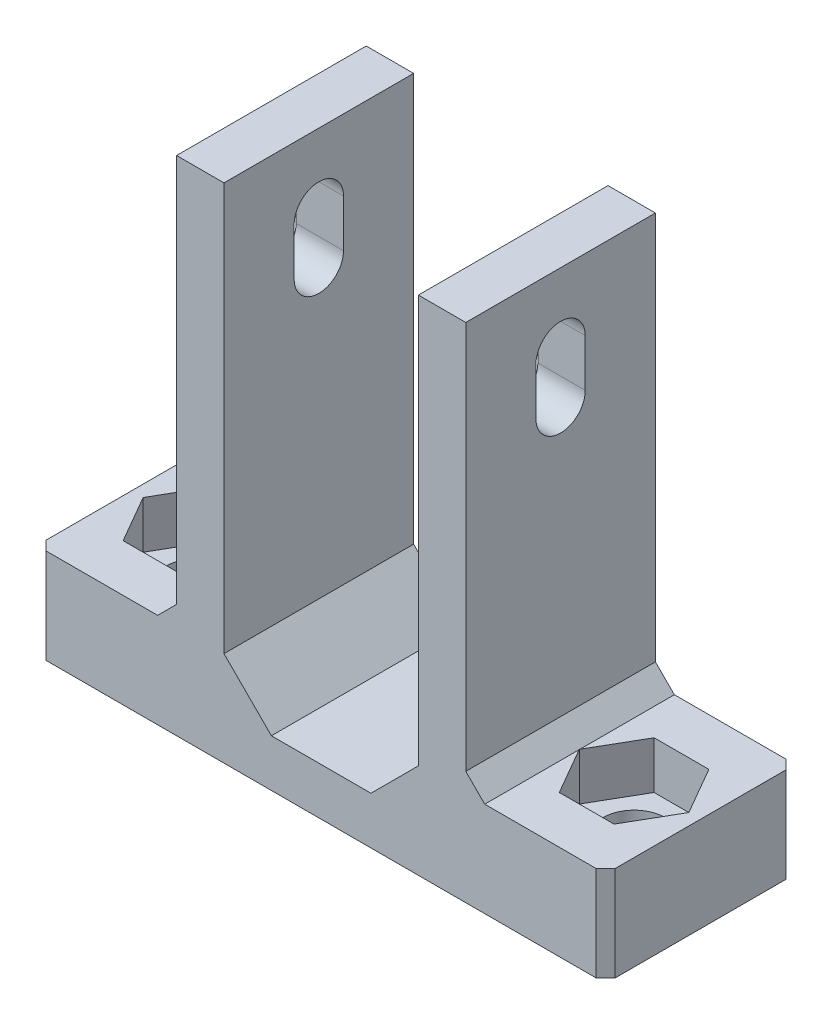
SolidWorks part; units mm, degrees
ref_plane "Front Plane" through (0, 0, 0) normal (0, 0, 1) x (1, 0, 0)
ref_plane "Top Plane" through (0, 0, 0) normal (0, 1, 0) x (1, 0, 0)
ref_plane "Right Plane" through (0, 0, 0) normal (1, 0, 0) x (0, 0, -1)
sketch "Sketch2" plane through (0, 0, 0) normal (0, 1, 0) x (1, 0, 0)
  line L1 (-30, 10) -> (30, 10)
  line L2 (-30, 10) -> (-30, -10)
  line L3 (-30, -10) -> (30, -10)
  line L4 (30, 10) -> (30, -10)
  line L5 (-30, 10) -> (30, -10) construction
  line L6 (-30, -10) -> (30, 10) construction
  circle A0 centre (-23, 0) radius 3.3
  circle A1 centre (23, 0) radius 3.3
  point P0 (0, 0)
  point P10 (0, 0)
  point P11 (0, 0)
  point P12 (0, 0)
  dimension "D5" = 6.6
  dimension "D1" = 20
  dimension "D2" = 60
  dimension "D3" = 46
  dimension "D4" = 23
extrude "Boss-Extrude2" add sketch "Sketch2" along normal blind 5
sketch "Sketch3" plane through (0, 0, 10) normal (0, 0, 1) x (1, 0, 0)
  line L0 (-30, 5) -> (30, 5) construction
  line L1 (-15.25, 5) -> (-10.25, 5)
  line L2 (-15.25, 5) -> (-15.25, 53)
  line L3 (-15.25, 53) -> (-10.25, 53)
  line L4 (-10.25, 5) -> (-10.25, 53)
  line L5 (0, 0) -> (0, -12.3291) construction
  line L6 (10.25, 5) -> (15.25, 5)
  line L7 (10.25, 5) -> (10.25, 53)
  line L8 (10.25, 53) -> (15.25, 53)
  line L9 (15.25, 5) -> (15.25, 53)
  dimension "D1" = 20.5
  dimension "D2" = 5
  dimension "D3" = 48
extrude "Boss-Extrude3" add sketch "Sketch3" against normal up to surface (20 mm away) up to face at (0, 2.5, -10)
sketch "Sketch4" plane through (15.25, 0, 0) normal (1, 0, 0) x (0, 0, -1)
  line L0 (0, 45.5) -> (0, 40.5) construction
  line L1 (2.6, 45.5) -> (2.6, 40.5)
  line L2 (-2.6, 45.5) -> (-2.6, 40.5)
  line L3 (10, 53) -> (-10, 53) construction
  arc A0 (2.6, 45.5) -> (-2.6, 45.5) centre (0, 45.5) ccw
  arc A1 (-2.6, 40.5) -> (2.6, 40.5) centre (0, 40.5) ccw
  point P3 (0, 43)
  dimension "D1" = 5.2
  dimension "D2" = 10
  dimension "D3" = 5
extrude "Cut-Extrude1" cut sketch "Sketch4" against normal up to surface (30.5 mm away) up to face at (-15.25, 29, 0)
sketch "Sketch5" plane through (0, 5, 0) normal (0, 1, 0) x (1, 0, 0)
  line L0 (30, 10) -> (15.25, 10) construction
  line L1 (15.25, 10) -> (15.25, -10) construction
  line L2 (15.25, -10) -> (30, -10) construction
  line L3 (30, -10) -> (30, 10) construction
  line L4 (-15.25, -10) -> (-15.25, 10) construction
  line L5 (-15.25, 10) -> (-30, 10) construction
  line L6 (-30, 10) -> (-30, -10) construction
  line L7 (-30, -10) -> (-15.25, -10) construction
  line L8 (30, 10) -> (15.25, 10)
  line L9 (15.25, 10) -> (15.25, -10)
  line L10 (15.25, -10) -> (30, -10)
  line L11 (30, -10) -> (30, 10)
  line L12 (-15.25, -10) -> (-15.25, 10)
  line L13 (-15.25, 10) -> (-30, 10)
  line L14 (-30, 10) -> (-30, -10)
  line L15 (-30, -10) -> (-15.25, -10)
  line L17 (-17.2265, 0) -> (-20.1132, 5)
  line L18 (-20.1132, 5) -> (-25.8868, 5)
  line L19 (-25.8868, 5) -> (-28.7735, 0)
  line L20 (-28.7735, 0) -> (-25.8868, -5)
  line L21 (-25.8868, -5) -> (-20.1132, -5)
  line L22 (-20.1132, -5) -> (-17.2265, 0)
  line L23 (28.7735, 0) -> (25.8868, 5)
  line L24 (25.8868, 5) -> (20.1132, 5)
  line L25 (20.1132, 5) -> (17.2265, 0)
  line L26 (17.2265, 0) -> (20.1132, -5)
  line L27 (20.1132, -5) -> (25.8868, -5)
  line L28 (25.8868, -5) -> (28.7735, 0)
  circle A0 centre (-23, 0) radius 5 construction
  circle A1 centre (23, 0) radius 5 construction
  point P18 (0, 0)
  dimension "D1" = 10
  dimension "D2" = 10
extrude "Boss-Extrude4" add sketch "Sketch5" along normal blind 5
chamfer "Chamfer1" distance 2 angle 45 2 edges at (15.25, 10, 0) (-15.25, 10, 0)
chamfer "Chamfer2" distance 5 angle 45 2 edges at (10.25, 5, 0) (-10.25, 5, 0)
chamfer "Chamfer3" distance 1 angle 45 4 edges at (30, 5, -10) (-30, 5, -10) (30, 5, 10) (-30, 5, 10)
